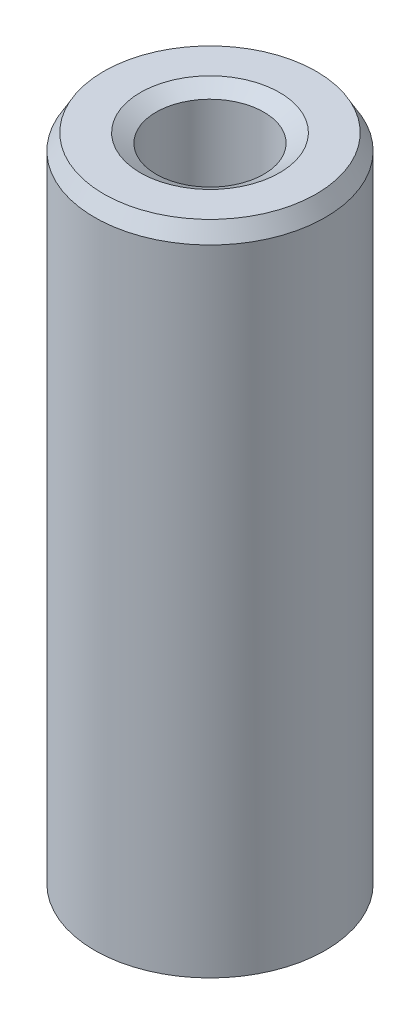
SolidWorks part; units mm, degrees
ref_plane "Front Plane" through (0, 0, 0) normal (0, 0, 1) x (1, 0, 0)
ref_plane "Top Plane" through (0, 0, 0) normal (0, 1, 0) x (1, 0, 0)
ref_plane "Right Plane" through (0, 0, 0) normal (1, 0, 0) x (0, 0, -1)
sketch "Sketch1" plane through (0, 0, 0) normal (0, 1, 0) x (1, 0, 0)
  circle A0 centre (0, 0) radius 5
  dimension "SLEEVE_OD" = 10
extrude "Boss-Extrude1" add sketch "Sketch1" along normal blind 28.5898
sketch "Sketch2" plane through (0, 0, 0) normal (0, 1, 0) x (1, 0, 0)
  circle A0 centre (0, 0) radius 2.3341
  dimension "BORE_D" = 4.6681
extrude "Cut-Extrude1" cut sketch "Sketch2" along normal through all
chamfer "Chamfer1" distance 0.6832 angle 30 4 edges at (0, 28.5898, 2.3341) (0, 0, 2.3341) (0, 0, 5) (0, 28.5898, 5) first distance on face at (0, 28.5898, 2.3341) first distance on face at (0, 0, 2.3341) first distance on face at (0, 28.5898, 5)
